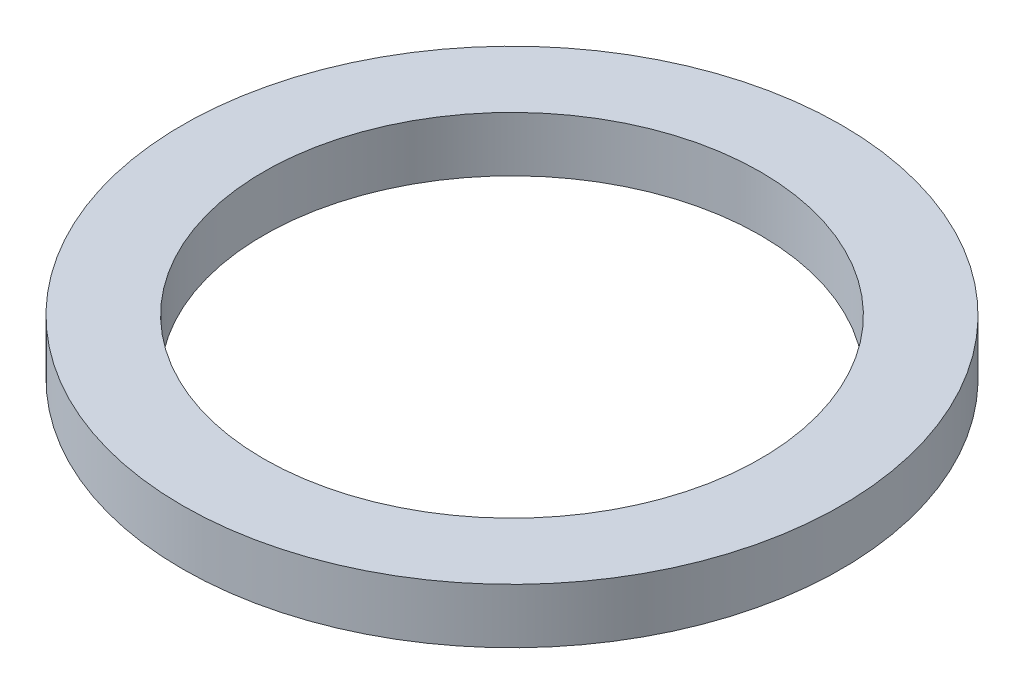
SolidWorks part; units mm, degrees
ref_plane "Front Plane" through (0, 0, 0) normal (0, 0, 1) x (1, 0, 0)
ref_plane "Top Plane" through (0, 0, 0) normal (0, 1, 0) x (1, 0, 0)
ref_plane "Right Plane" through (0, 0, 0) normal (1, 0, 0) x (0, 0, -1)
sketch "Sketch1" plane through (0, 0, 0) normal (0, 1, 0) x (1, 0, 0)
  circle A0 centre (0, 0) radius 28.7274
  circle A1 centre (0, 0) radius 38.1
  dimension "D1" = 57.4548
  dimension "D2" = 76.2
extrude "Boss-Extrude1" add sketch "Sketch1" along normal blind 6.35
